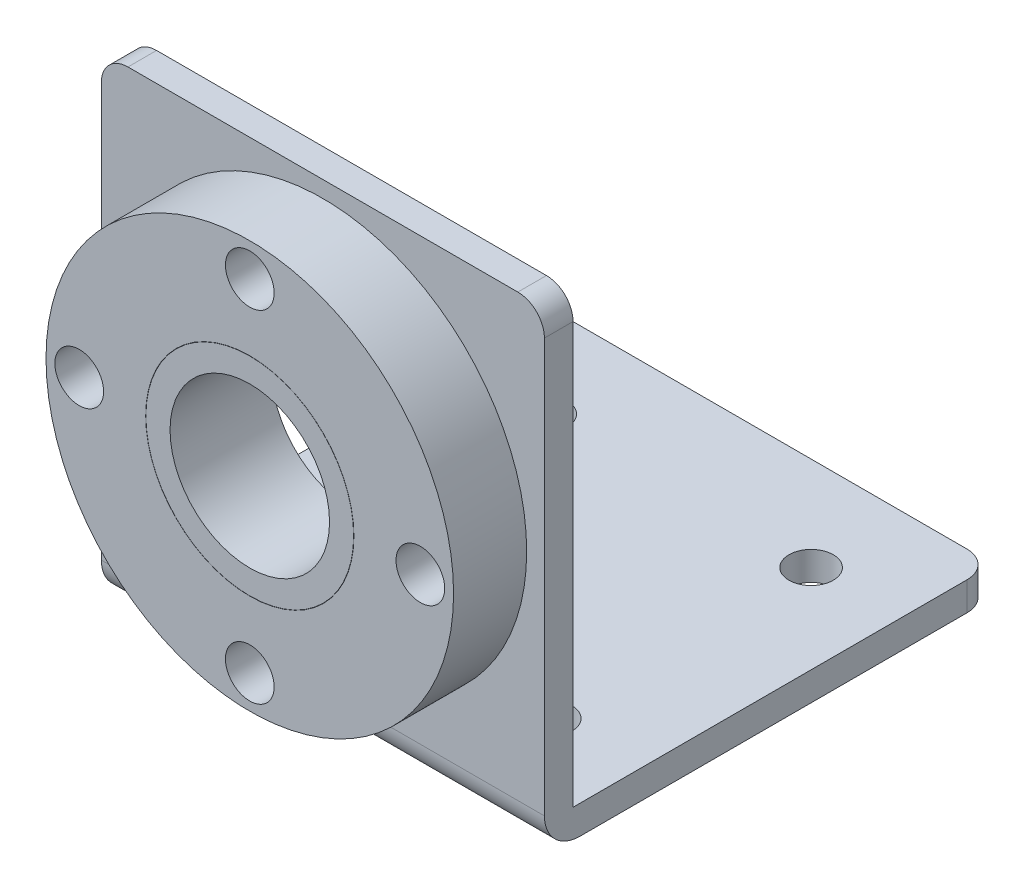
SolidWorks part; units mm, degrees
ref_plane "Front Plane" through (0, 0, 0) normal (0, 0, 1) x (1, 0, 0)
ref_plane "Top Plane" through (0, 0, 0) normal (0, 1, 0) x (1, 0, 0)
ref_plane "Right Plane" through (0, 0, 0) normal (1, 0, 0) x (0, 0, -1)
sketch "Sketch1" plane through (0, 0, 0) normal (0, 1, 0) x (1, 0, 0)
  line L0 (-25, 0) -> (25, 0) construction
  line L1 (-25, -25.35) -> (25, -25.35)
  line L2 (-25, -25.35) -> (-25, 25.35)
  line L3 (-25, 25.35) -> (25, 25.35)
  line L4 (25, -25.35) -> (25, 25.35)
  line L5 (-25, -25.35) -> (25, 25.35) construction
  line L6 (-25, 25.35) -> (25, -25.35) construction
  line L7 (0, 25.35) -> (0, -25.35) construction
  circle A0 centre (15, -14.75) radius 2.5
  circle A1 centre (15, 14.75) radius 2.5
  circle A2 centre (-15, -14.75) radius 2.5
  circle A3 centre (-15, 14.75) radius 2.5
  point P0 (0, 0)
  dimension "D3" = 15
  dimension "D4" = 14.75
  dimension "D5" = 5
  dimension "D1" = 50.7
  dimension "D2" = 50
extrude "Boss-Extrude1" add sketch "Sketch1" along normal blind 3.23
sketch "Sketch2" plane through (0, 3.23, 0) normal (0, 1, 0) x (1, 0, 0)
  line L0 (25, -25.35) -> (25, 25.35) construction
  line L1 (-25, -25.35) -> (25, -25.35)
  line L2 (-25, -25.35) -> (-25, -22.12)
  line L3 (-25, -22.12) -> (25, -22.12)
  line L4 (25, -25.35) -> (25, -22.12)
  dimension "D1" = 3.23
extrude "Boss-Extrude2" add sketch "Sketch2" along normal blind 50.47
fillet "Fillet1" radius 4 1 edges at (0, 0, 25.35)
fillet "Fillet2" radius 3 4 edges at (-25, 1.615, -25.35) (25, 1.615, -25.35) (-25, 53.7, 23.735) (25, 53.7, 23.735)
sketch "Sketch4" plane through (0, 0, 25.35) normal (0, 0, 1) x (1, 0, 0)
  line L0 (0, 53.7) -> (0, 0) construction
  line L1 (-22, 53.7) -> (22, 53.7) construction
  circle A0 centre (0, 28.85) radius 23
  circle A1 centre (0, 48.1) radius 2.75
  circle A2 centre (19.25, 28.85) radius 2.75
  circle A3 centre (0, 9.6) radius 2.75
  circle A4 centre (-19.25, 28.85) radius 2.75
  circle A5 centre (0, 28.85) radius 11.75
  point P18 (0, 28.85)
  dimension "D1" = 46
  dimension "D3" = 5.5
  dimension "D6" = 23.5
  dimension "D2" = 24.85
  dimension "D4" = 19.25
  dimension "D5" = 4
extrude "Cut-Extrude1" cut sketch "Sketch4" against normal through all both and the other way through all contours A4 | A2 | A1 | A3 | A5 region at (19.25, 28.85, 25.35) region at (-19.25, 28.85, 25.35)
extrude "Boss-Extrude3" add sketch "Sketch4<3>" along normal blind 8.25 contours A0 L0 A1 A5 A3 A2 | L0 A0 A3 A5 A1 A4 region at (15.8998, 44.7498, 25.35) region at (-0.5143, 51.35, 25.35)
sketch "Sketch4<3>" plane through (0, 0, 25.35) normal (0, 0, 1) x (1, 0, 0) same geometry as "Sketch4"
sketch "Sketch5" plane through (0, 0, 22.12) normal (0, 0, -1) x (-1, 0, 0)
  circle A0 centre (0, 28.85) radius 11.725
  circle A1 centre (0, 28.85) radius 9
  dimension "D1" = 23.45
  dimension "D2" = 18
extrude "Boss-Extrude4" add sketch "Sketch5" against normal up to surface (11.48 mm away) separate body up to face at (2.75, 48.1, 33.6)
